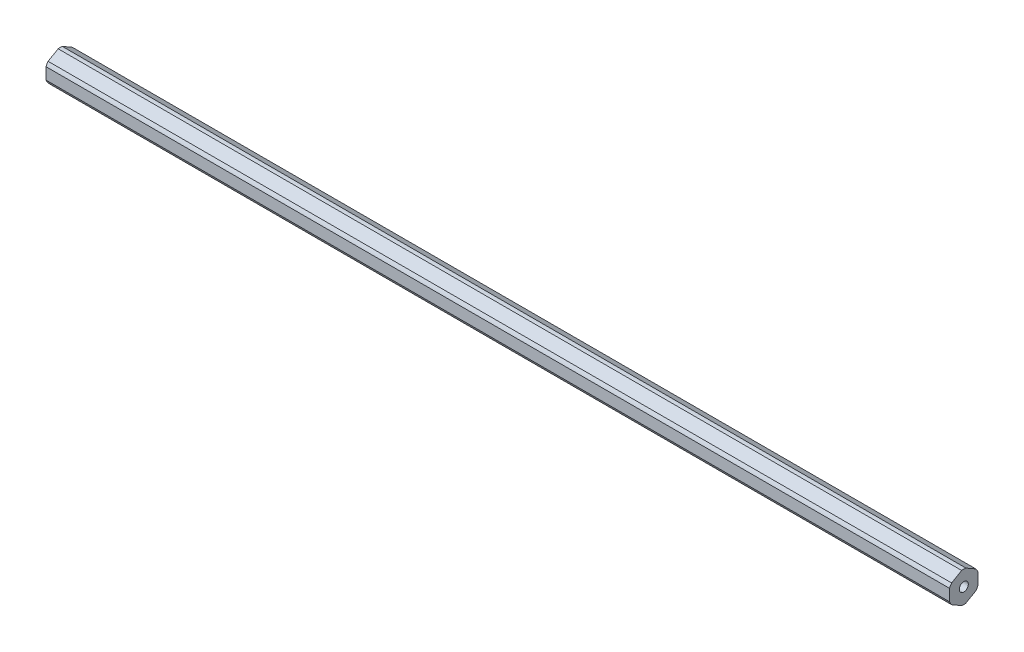
SolidWorks part; units mm, degrees
material "7075-T6 (SN)"
ref_plane "Front Plane" through (0, 0, 0) normal (0, 0, 1) x (1, 0, 0)
ref_plane "Top Plane" through (0, 0, 0) normal (0, 1, 0) x (1, 0, 0)
ref_plane "Right Plane" through (0, 0, 0) normal (1, 0, 0) x (0, 0, -1)
sketch "Sketch1" plane through (0, 0, 0) normal (1, 0, 0) x (0, 0, -1)
  line L1 (0, 7.3323) -> (-6.35, 3.6662)
  line L2 (-6.35, 3.6662) -> (-6.35, -3.6662)
  line L3 (-6.35, -3.6662) -> (0, -7.3323)
  line L4 (0, -7.3323) -> (6.35, -3.6662)
  line L5 (6.35, -3.6662) -> (6.35, 3.6662)
  line L6 (6.35, 3.6662) -> (0, 7.3323)
  circle A1 centre (0, 0) radius 6.35
  circle A2 centre (0, 0) radius 6.35 construction
  circle A3 centre (0, 0) radius 6.858
  dimension "D1" = 12.7
  dimension "D2" = 12.7
  dimension "D3" = 13.716
extrude "Boss-Extrude1" add sketch "Sketch1" along normal mid plane 403.1615 contours A1 | L6 A3 L1 A1 | L5 A3 L6 A1 | L4 A3 L5 A1 | L3 A3 L4 A1 | L2 A3 L3 A1 | L1 A3 L2 A1 region at (0, 6.4568, 0) region at (0, 3.2284, 5.5918) region at (0, 0, 0) region at (0, 3.2284, -5.5918) region at (0, -3.2284, 5.5918) region at (0, -3.2284, -5.5918) region at (0, -6.4568, 0)
hole_wizard "#10-32 Tapped Hole1" positions "3DSketch1" profile "Sketch2" tap size "#10-32" standard "ANSI Inch"
sketch3d "3DSketch1"
  line L0 (201.5807, 0, 0) -> (-201.5807, 0, 0) construction
  point P11 (201.5807, 0, 0)
  point P25 (-201.5807, 0, 0)
sketch "Sketch2" plane through (201.5807, 0, 0) normal (0, 1, 0) x (0, 0, -1)
  line L0 (0, 0) -> (0, 13.2428)
  line L1 (0, 13.2428) -> (2.0193, 12.0294)
  line L2 (2.0193, 12.0294) -> (2.0193, 0)
  line L5 (2.0193, 0) -> (0, 0)
  line L10 (0, 13.2428) -> (-2.0193, 12.0294) construction
  line L11 (0, -6.35) -> (0, 107.95) construction
  dimension "Tap Drill Dia." = 4.0386
  dimension "Tap Drill Depth" = 12.0294
  dimension "Drill Angle" = 118
cosmetic thread "Hole Thread1" parameters "D1"=13.97, "D2"=4.826
cosmetic thread "Hole Thread2" parameters "D1"=13.97, "D2"=4.826
sketch "Sketch3" plane through (0, 0, 0) normal (0, 1, 0) x (1, 0, 0)
  line L0 (0, 0) -> (162.634, 0) construction
  line L2 (185.5788, -5.842) -> (186.5948, -5.842)
  line L3 (185.5788, -5.842) -> (185.5788, -13.6186)
  line L4 (185.5788, -13.6186) -> (186.5948, -13.6186)
  line L5 (186.5948, -5.842) -> (186.5948, -13.6186)
  line L7 (201.5807, -6.35) -> (201.5807, -5.4183) construction
  dimension "D1" = 1.016
  dimension "D2" = 5.842
  dimension "D3" = 14.986
